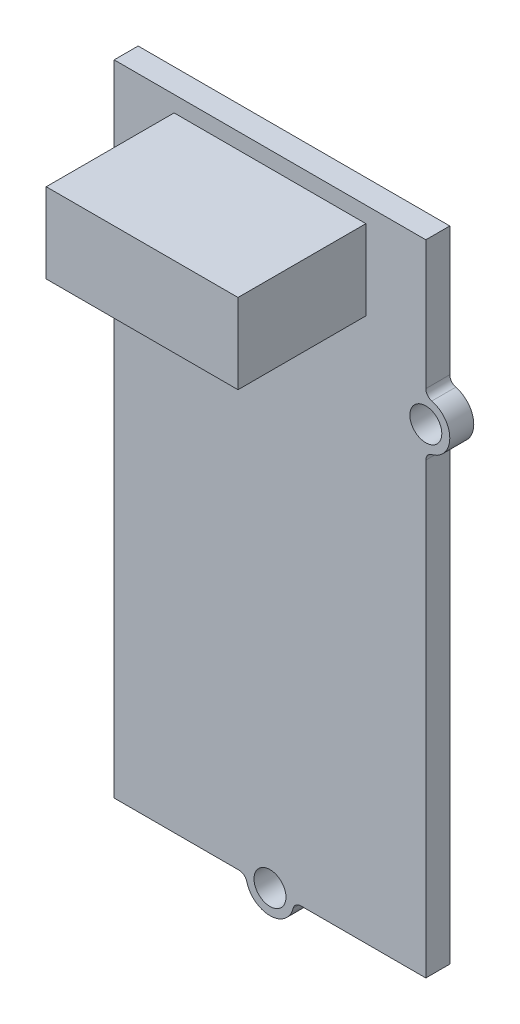
SolidWorks part; units mm, degrees
ref_plane "正面" through (0, 0, 0) normal (0, 0, 1) x (1, 0, 0)
ref_plane "平面" through (0, 0, 0) normal (0, 1, 0) x (1, 0, 0)
ref_plane "右側面" through (0, 0, 0) normal (1, 0, 0) x (0, 0, -1)
sketch "ｽｹｯﾁ1" plane through (0, 0, 0) normal (0, 0, 1) x (1, 0, 0)
  line L1 (-9.75, -20) -> (9.75, -20)
  line L2 (-9.75, -20) -> (-9.75, 20)
  line L3 (-9.75, 20) -> (9.75, 20)
  line L4 (9.75, -20) -> (9.75, 20)
  line L5 (-9.75, -20) -> (9.75, 20) construction
  line L6 (-9.75, 20) -> (9.75, -20) construction
  point P0 (0, 0)
  dimension "D1" = 19.5
  dimension "D2" = 40
extrude "ﾎﾞｽ - 押し出し1" add sketch "ｽｹｯﾁ1" along normal blind 1.5
sketch "ｽｹｯﾁ2" plane through (0, 0, 1.5) normal (0, 0, 1) x (1, 0, 0)
  line L0 (9.75, -20) -> (9.75, 20) construction
  line L1 (-9.75, 20) -> (-9.75, -20) construction
  line L2 (9.75, 20) -> (-9.75, 20) construction
  line L3 (-9.75, -20) -> (9.75, -20) construction
  circle A0 centre (9.75, 10) radius 1.5
  circle A1 centre (-9.75, 10) radius 1.5
  circle A2 centre (0, -20) radius 1.5
  dimension "D1" = 10
  dimension "D2" = 10
  dimension "D3" = 3
  dimension "D4" = 3
  dimension "D5" = 3
extrude "ﾎﾞｽ - 押し出し2" add sketch "ｽｹｯﾁ2" against normal blind 1.5
sketch "ｽｹｯﾁ3" plane through (0, 0, 1.5) normal (0, 0, 1) x (1, 0, 0)
  circle A0 centre (-9.75, 10) radius 1
  circle A1 centre (9.75, 10) radius 1
  circle A2 centre (0, -20) radius 1
  dimension "D1" = 2
  dimension "D2" = 2
  dimension "D3" = 2
extrude "ｶｯﾄ - 押し出し1" cut sketch "ｽｹｯﾁ3" against normal blind 1.5
fillet "ﾌｨﾚｯﾄ1" radius 0.5 6 edges at (-9.75, 8.5, 0.75) (-9.75, 11.5, 0.75) (9.75, 8.5, 0.75) (9.75, 11.5, 0.75) (-1.5, -20, 0.75) (1.5, -20, 0.75)
sketch "ｽｹｯﾁ4" plane through (0, 0, 1.5) normal (0, 0, 1) x (1, 0, 0)
  line L0 (9.75, 20) -> (-9.75, 20) construction
  line L1 (-6, 19) -> (6, 19)
  line L2 (-6, 19) -> (-6, 14)
  line L3 (-6, 14) -> (6, 14)
  line L4 (6, 19) -> (6, 14)
  point P6 (0, 19)
  point P7 (0, 20)
  dimension "D1" = 1
  dimension "D2" = 12
  dimension "D3" = 0
  dimension "D4" = 5
extrude "ﾎﾞｽ - 押し出し3" add sketch "ｽｹｯﾁ4" along normal blind 8
